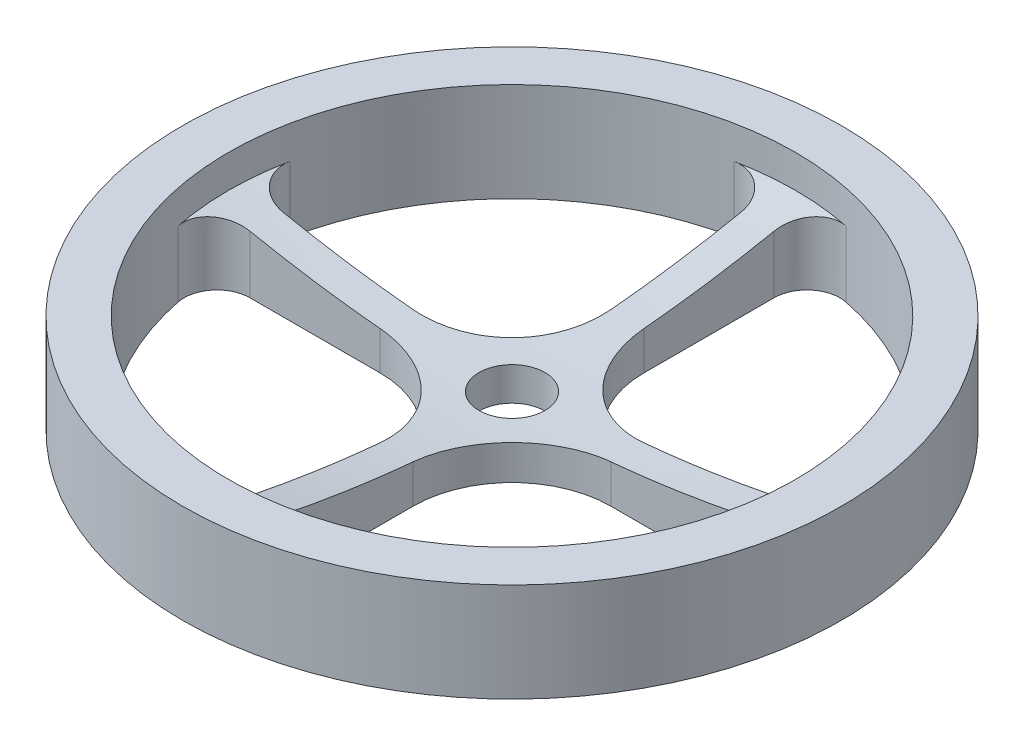
SolidWorks part; units mm, degrees
ref_plane "Plane1" through (0, 0, 0) normal (0, 0, 1) x (1, 0, 0)
ref_plane "Plane2" through (0, 0, 0) normal (0, 1, 0) x (1, 0, 0)
ref_plane "Plane3" through (0, 0, 0) normal (1, 0, 0) x (0, 0, -1)
sketch "Sketch1" plane through (0, 0, 0) normal (0, 1, 0) x (1, 0, 0)
  circle A0 centre (0, 0) radius 12.7
  dimension "D1" = 25.4
extrude "Thread Blank" add sketch "Sketch1" along normal blind 3.81
sketch "Sketch2" plane through (0, 3.81, 0) normal (0, 1, 0) x (-1, 0, 0)
  circle A0 centre (0, 0) radius 12.7 construction
  circle A1 centre (0, 0) radius 12.7
curve "Helix1" pitch 1.27 height 5.08 turns 4
sketch "Sketch3" plane through (0, 0, 0) normal (0, 0, 1) x (1, 0, 0)
  line L0 (12.7025, 5.0283) -> (12.7025, 3.81)
  line L1 (12.7025, 3.81) -> (11.4325, 4.4191)
  line L2 (11.4325, 4.4191) -> (12.7025, 5.0283)
  line L3 (12.7, 0) -> (12.7, 3.81) construction
  dimension "D1" = 1.27
  dimension "D2" = 1.2183
  dimension "D3" = 0.0025
sweep "Thread" [suppressed] cut profiles "Sketch3" path "Helix1"
sketch "Sketch4" plane through (0, 0, 0) normal (0, 0, 1) x (1, 0, 0)
  line L0 (0, 0) -> (0, 5.8973) construction
  line L1 (0, 3.81) -> (10.922, 3.81)
  line L2 (10.922, 3.81) -> (10.922, 2.54)
  line L3 (12.7, 3.81) -> (-12.7, 3.81) construction
  line L5 (0, 3.81) -> (0, 1.27)
  line L6 (12.7, 0) -> (-12.7, 0) construction
  arc A0 (10.922, 2.54) -> (0, 1.27) centre (0, 48.8696) cw
  point P10 (10.922, 3.81)
  point P11 (-10.922, 3.81)
  dimension "D1" = 21.844
  dimension "D2" = 1.27
  dimension "D3" = 2.54
revolve "Center Depression" cut sketch "Sketch4" angle 360 about L0
sketch "Sketch5" plane through (0, 0, 0) normal (0, 1, 0) x (1, 0, 0)
  line L0 (0, 0) -> (15.0646, 0) construction
  line L1 (0, 0) -> (0, 13.3345) construction
  line L2 (0.635, 9.4621) -> (0.635, 4.445)
  line L3 (4.445, 0.635) -> (9.4621, 0.635)
  line L4 (-4.445, 0.635) -> (-9.4621, 0.635)
  line L5 (-0.635, 9.4621) -> (-0.635, 4.445)
  line L6 (-0.635, -9.4621) -> (-0.635, -4.445)
  line L7 (-4.445, -0.635) -> (-9.4621, -0.635)
  line L8 (4.445, -0.635) -> (9.4621, -0.635)
  line L9 (0.635, -9.4621) -> (0.635, -4.445)
  arc A0 (10.7072, 2.1557) -> (2.1557, 10.7072) centre (0, 0) ccw
  arc A1 (2.1557, 10.7072) -> (0.635, 9.4621) centre (1.905, 9.4621) ccw
  arc A2 (9.4621, 0.635) -> (10.7072, 2.1557) centre (9.4621, 1.905) ccw
  arc A3 (4.445, 0.635) -> (0.635, 4.445) centre (4.445, 4.445) cw
  arc A4 (-4.445, 0.635) -> (-0.635, 4.445) centre (-4.445, 4.445) ccw
  arc A5 (-9.4621, 0.635) -> (-10.7072, 2.1557) centre (-9.4621, 1.905) cw
  arc A6 (-2.1557, 10.7072) -> (-0.635, 9.4621) centre (-1.905, 9.4621) cw
  arc A7 (-10.7072, 2.1557) -> (-2.1557, 10.7072) centre (0, 0) cw
  arc A8 (-10.7072, -2.1557) -> (-2.1557, -10.7072) centre (0, 0) ccw
  arc A9 (-2.1557, -10.7072) -> (-0.635, -9.4621) centre (-1.905, -9.4621) ccw
  arc A10 (-9.4621, -0.635) -> (-10.7072, -2.1557) centre (-9.4621, -1.905) ccw
  arc A11 (-4.445, -0.635) -> (-0.635, -4.445) centre (-4.445, -4.445) cw
  arc A12 (4.445, -0.635) -> (0.635, -4.445) centre (4.445, -4.445) ccw
  arc A13 (9.4621, -0.635) -> (10.7072, -2.1557) centre (9.4621, -1.905) cw
  arc A14 (2.1557, -10.7072) -> (0.635, -9.4621) centre (1.905, -9.4621) cw
  arc A15 (10.7072, -2.1557) -> (2.1557, -10.7072) centre (0, 0) cw
  circle A16 centre (0, 0) radius 10.922 construction
  dimension "D1" = 1.27
  dimension "D2" = 1.27
  dimension "D3" = 3.81
  dimension "D4" = 1.27
extrude "Vent" cut sketch "Sketch5" along normal through all
sketch "Sketch6" plane through (0, 0, 0) normal (0, 1, 0) x (1, 0, 0)
  circle A0 centre (0, 0) radius 1.27
  dimension "D1" = 2.54
extrude "Center Hole" cut sketch "Sketch6" along normal through all
